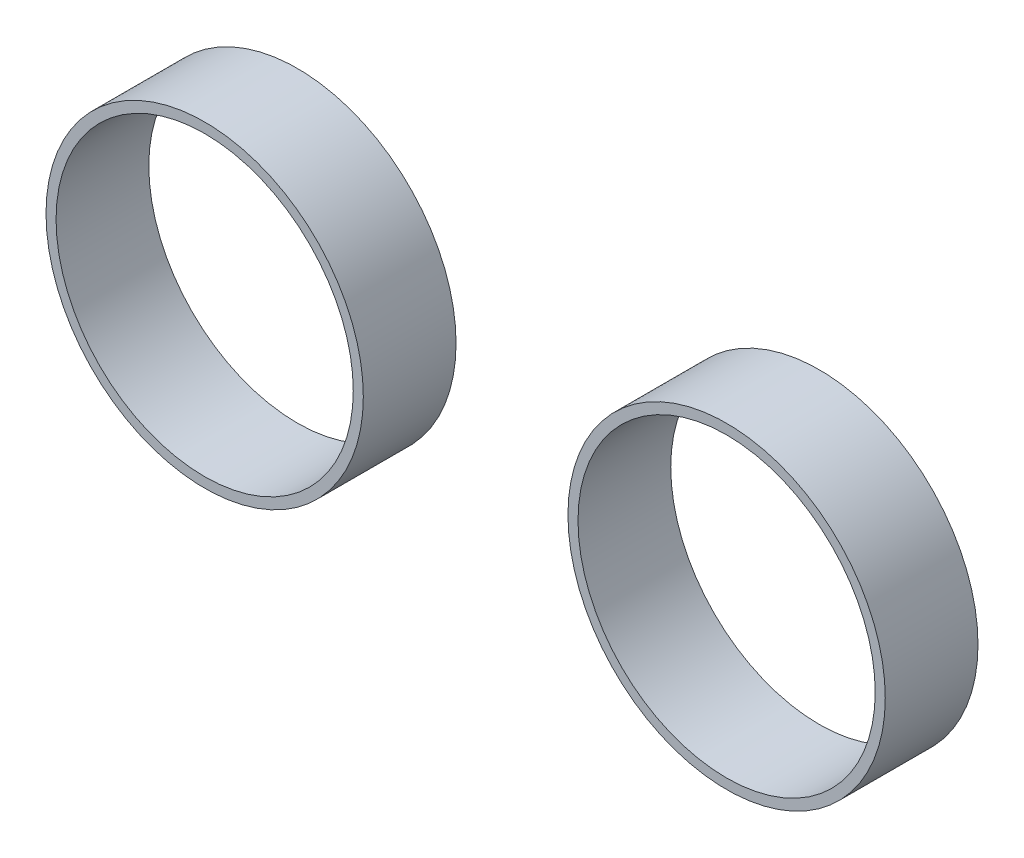
SolidWorks part; units mm, degrees
material "Velcro"
ref_plane "Front Plane" through (0, 0, 0) normal (0, 0, 1) x (1, 0, 0)
ref_plane "Top Plane" through (0, 0, 0) normal (0, 1, 0) x (1, 0, 0)
ref_plane "Right Plane" through (0, 0, 0) normal (1, 0, 0) x (0, 0, -1)
sketch "Sketch1" plane through (0, 0, 0) normal (0, 0, 1) x (1, 0, 0)
  circle A0 centre (1435.9805, -423.3823) radius 65
  circle A1 centre (1435.9805, -423.3823) radius 69.4
  circle A2 centre (1664.2805, -423.3823) radius 65
  circle A3 centre (1664.2805, -423.3823) radius 69.4
  dimension "D1" = 130
  dimension "D3" = 130
  dimension "D4" = 4.4
  dimension "D2" = 4.4
extrude "Boss-Extrude1" add sketch "Sketch1" along normal blind 40.56
